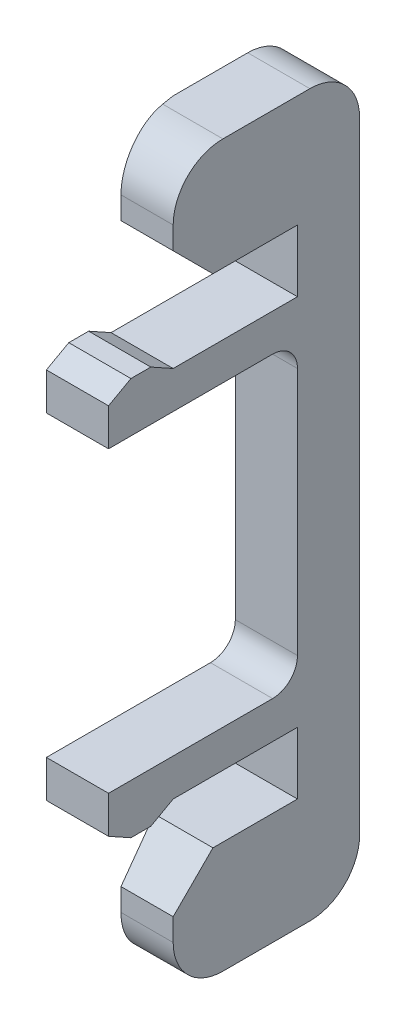
SolidWorks part; units mm, degrees
ref_plane "Front Plane" through (0, 0, 0) normal (0, 0, 1) x (1, 0, 0)
ref_plane "Top Plane" through (0, 0, 0) normal (0, 1, 0) x (1, 0, 0)
ref_plane "Right Plane" through (0, 0, 0) normal (1, 0, 0) x (0, 0, -1)
sketch "Sketch1" plane through (0, 0, 0) normal (0, 0, 1) x (1, 0, 0)
  line L1 (-1.5875, -18.415) -> (1.5875, -18.415)
  line L2 (-1.5875, -18.415) -> (-1.5875, 18.415)
  line L3 (-1.5875, 18.415) -> (1.5875, 18.415)
  line L4 (1.5875, -18.415) -> (1.5875, 18.415)
  line L5 (-1.5875, -18.415) -> (1.5875, 18.415) construction
  line L6 (-1.5875, 18.415) -> (1.5875, -18.415) construction
  point P0 (0, 0)
  dimension "D1" = 36.83
  dimension "D2" = 3.175
extrude "Base" add sketch "Sketch1" along normal blind 3.175
sketch "Sketch3" plane through (-1.5875, 0, 0) normal (-1, 0, 0) x (0, 0, 1)
  line L0 (3.175, 12.7) -> (9.525, 12.7)
  line L1 (3.175, 18.415) -> (3.175, -18.415) construction
  line L3 (3.175, -12.7) -> (9.525, -12.7)
  line L5 (3.175, 18.415) -> (3.175, 12.7)
  line L6 (3.175, -12.7) -> (3.175, -18.415)
  line L7 (3.175, 18.415) -> (9.525, 18.415)
  line L9 (3.175, -18.415) -> (9.525, -18.415)
  line L10 (9.525, -18.415) -> (9.525, -12.7)
  line L11 (9.525, 18.415) -> (9.525, 12.7)
  dimension "D1" = 6.35
  dimension "D2" = 25.4
extrude "Retainer" add sketch "Sketch3" against normal up to surface (3.175 mm away) up to face at (1.5875, 0, 1.5875)
sketch "Sketch5" plane through (-1.5875, 0, 0) normal (-1, 0, 0) x (0, 0, 1)
  line L0 (3.175, 9.525) -> (9.525, 9.525)
  line L1 (3.175, 12.7) -> (3.175, -12.7) construction
  line L2 (9.525, 9.525) -> (10.668, 10.16)
  line L3 (10.668, 10.16) -> (11.684, 10.16)
  line L4 (11.684, 10.16) -> (12.827, 9.525)
  line L5 (12.827, 9.525) -> (12.827, 7.62)
  line L6 (12.827, 7.62) -> (3.175, 7.62)
  line L7 (3.175, 9.525) -> (12.827, 9.525) construction
  line L8 (3.175, 12.7) -> (9.525, 12.7) construction
  line L9 (3.175, 0) -> (18.8887, 0) construction
  line L10 (3.175, -9.525) -> (12.827, -9.525) construction
  line L11 (12.827, -7.62) -> (3.175, -7.62)
  line L12 (12.827, -9.525) -> (12.827, -7.62)
  line L13 (11.684, -10.16) -> (12.827, -9.525)
  line L14 (10.668, -10.16) -> (11.684, -10.16)
  line L15 (9.525, -9.525) -> (10.668, -10.16)
  line L16 (3.175, -9.525) -> (9.525, -9.525)
  line L17 (3.175, 9.525) -> (3.175, 7.62)
  line L18 (3.175, -7.62) -> (3.175, -9.525)
  dimension "D1" = 6.35
  dimension "D2" = 1.905
  dimension "D3" = 1.016
  dimension "D4" = 9.652
  dimension "D5" = 0.635
  dimension "D6" = 3.175
extrude "Tab" add sketch "Sketch5" against normal up to surface (3.175 mm away) up to face at (1.5875, 0, 5.5562)
fillet "Fillet1" radius 1.27 2 edges at (0, -7.62, 3.175) (0, 7.62, 3.175)
fillet "Fillet2" radius 2.54 4 edges at (0, 18.415, 0) (0, -18.415, 0) (0, -18.415, 9.525) (0, 18.415, 9.525)
chamfer "Chamfer1" distance 2.032 angle 45 2 edges at (0, -12.7, 9.525) (0, 12.7, 9.525)
sketch "Sketch6" plane through (0, 18.415, 0) normal (0, 1, 0) x (1, 0, 0)
  line L0 (-1.5875, -6.35) -> (-1.0795, -9.525)
  line L1 (-1.5875, -6.985) -> (-1.5875, -2.54) construction
  line L2 (-1.0795, -9.525) -> (-1.5875, -9.525)
  line L3 (-1.5875, -9.525) -> (-1.5875, -6.35)
  line L4 (-1.5875, -9.525) -> (1.5875, -9.525) construction
  point P4 (0, 0)
  dimension "D1" = 3.175
  dimension "D2" = 0.508
extrude "Cut-Extrude1" cut sketch "Sketch6" against normal up to next
mirror "Mirror1" about plane through (0, 0, 0) normal (0, 1, 0) of "Cut-Extrude1"
